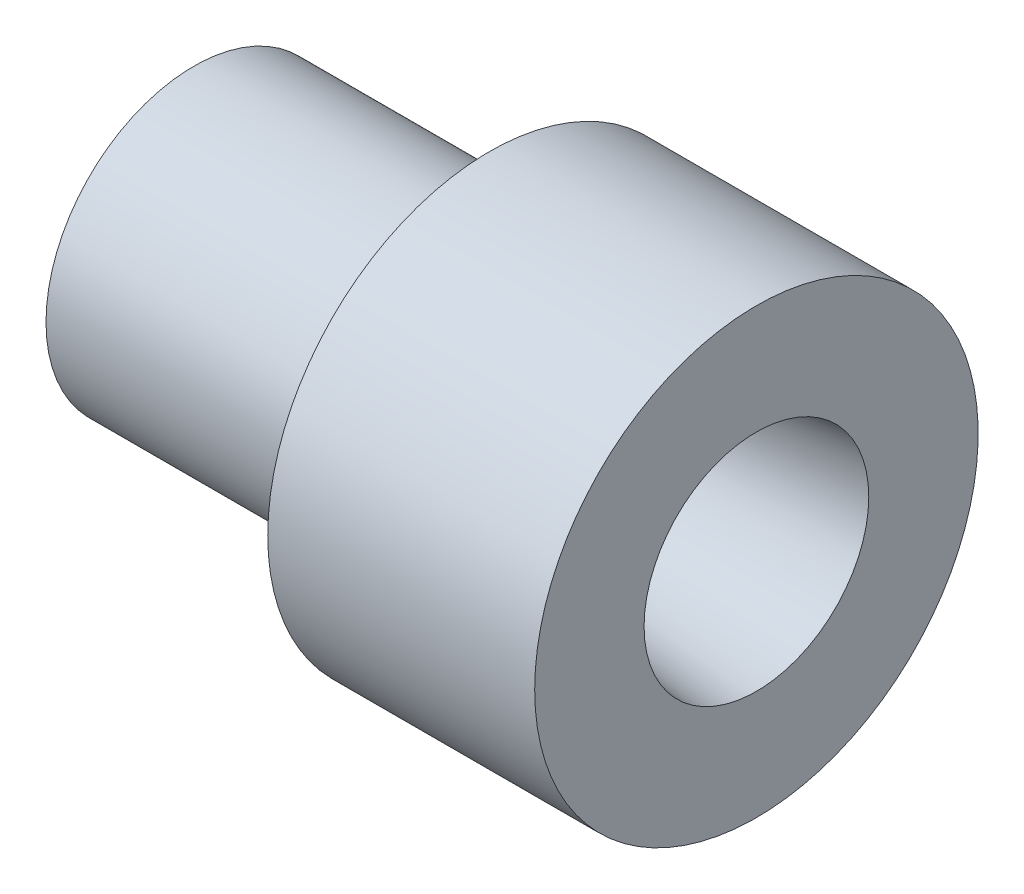
SolidWorks part; units mm, degrees
ref_plane "Front Plane" through (0, 0, 0) normal (0, 0, 1) x (1, 0, 0)
ref_plane "Top Plane" through (0, 0, 0) normal (0, 1, 0) x (1, 0, 0)
ref_plane "Right Plane" through (0, 0, 0) normal (1, 0, 0) x (0, 0, -1)
sketch "Sketch1" plane through (0, 0, 0) normal (0, 1, 0) x (1, 0, 0)
  line L0 (0, 0) -> (0, 2.286) construction
  line L1 (0, 2.286) -> (0, 6.35)
  line L2 (12.7, 9.525) -> (24.1665, 9.525)
  line L3 (24.1665, 9.525) -> (24.1665, 4.826)
  line L4 (24.1665, 4.826) -> (0, 2.286)
  line L5 (0, 0) -> (24.1665, 0) construction
  line L6 (24.1665, 0) -> (24.1665, 4.826) construction
  line L8 (12.7, 6.35) -> (12.7, 9.525)
  line L12 (0, 6.35) -> (12.7, 6.35)
  point P3 (0.1166, 6.35)
  point P6 (12.7, 6.35)
  point P11 (0, 6.35)
  point P12 (12.7, 7.1175)
  dimension "D1" = 2.286
  dimension "D2" = 4.826
  dimension "D3" = 6
  dimension "D4" = 9.525
  dimension "D5" = 6.35
  dimension "D6" = 12.7
revolve "Revolve1" add sketch "Sketch1" angle 360 about L5
equation "\"z\" = 8\t\t\t\t'number of blades"
equation "\"de\" = 0.43in\t\t\t'entrance eye diameter"
equation "\"de_length\" = 10mm\t\t'entrance eye consistent length"
equation "\"d_exit\" = 0.18in \t\t'throat aka d1"
equation "\"d2\" = 2.1in \t\t\t'outer diameter of the impeller"
equation "\"b2\" = .2in\t\t\t'tip height from disc surface at d2; slightly higher than d_exit"
equation "\"b1\" = \"b2\" + (\"d2\"/2 - \"de\"/2)*tan(\"theta\") \t\t\t'tip height from disc surface at inlet eye"
equation "\"theta\" = 12\t\t\t'angle of blades from inner to outer "
equation "\"ae\" = 3.14*(\"de\"^2)/4\t\t'entrance eye area'"
equation "\"ce\" = 3.14*\"de\"\t\t'entrance eye circumference"
equation "\"av_ratio\" = .325\t\t'ratio of av/ae at N_s of 470, range is .275 to .375, .325 ideal. High ratio means bigger area means smaller blades"
equation "\"av\" = \"ae\"*\"av_ratio\"\t\t'area between just two blades"
equation "\"s_open\" = \"av\"/\"b1\"\t\t'width of open area"
equation "\"s\"=\"ce\" - \"z\"*\"s_open\""
equation "\"min blade thickness\" = .15in"
equation "\"bearing OD\" = 30mm"
equation "\"bearing ID\"= 10mm"
equation "\"bearing depth\"= 9mm"
equation "\"bearing outer race thickness\"= 1mm"
equation "\"bearing inner race thickness\"= 1mm"
equation "\"bearing bore\" = \"bearing depth\" + 1mm"
equation "\"lower seal OD\" = .917in\t\t'this is https://www.mcmaster.com/#9281k121/=174001b"
equation "\"lower seal ID\"= .375in"
equation "\"lower seal depth\" = .625in + .218in"
equation "\"lower seal bore\" = \"lower seal depth\" + 1mm"
equation "\"upper seal OD\" = 1.125in\t'this is https://www.mcmaster.com/#5154t33/=173zuau, needs to be visually inspected before machining!"
equation "\"upper seal ID\"= 0.625in"
equation "\"upper seal depth\"= .25in\t'aka height; these values need to be confirmed by inspection!! We may want to compress the height."
equation "\"upper seal bore\" = \"upper seal depth\" + 1mm"
equation "\"big o-ring thickness\" = .139in"
equation "\"big o-ring OD\" = 2.734in"
equation "\"big o-ring ID\" = 3.012in"
equation "\"big o-ring groove depth\" = \"big o-ring thickness\"*4/5"
equation "\"impeller center height\" = \"impeller base thickness\" + \"b1\"\t'impeller height at de"
equation "\"impeller outer height\" = \"impeller base thickness\" + \"b2\"\t'impeller height at de"
equation "\"impeller upper clearance\"= .5mm"
equation "\"impeller horizontal clearance\"= (\"d2\"*1.15 - \"d2\")/2 \t\t'clearance based on D2-D3 ratio for circular volute, ranges 1.15 to 1.2"
equation "\"impeller bottom clearance\"= .5mm"
equation "\"impeller base thickness\"= 2mm"
equation "\"impeller dowel diameter\" = 2mm"
equation "\"impeller bolt head diameter\" = \"m4 head bore diameter\""
equation "\"impeller bolt head depth\" = 4mm"
equation "\"impeller bolt stop depth\" = 3mm"
equation "\"impeller bolt bore\" = \"m4 clearance\""
equation "\"impeller shaft bore depth\" = 12mm"
equation "\"impeller shaft bore\" = 8mm"
equation "\"impeller boss depth\" = \"impeller shaft bore depth\"+\"impeller bolt stop depth\"+\"impeller bolt head depth\"-\"impeller base thickness\""
equation "\"impeller boss diameter\" = \"upper seal ID\""
equation "\"impeller dowel length\" = 2mm*2 + \"impeller shaft bore\""
equation "\"coupler motor shaft hole ID\"= 8mm"
equation "\"coupler OD\"= 17mm"
equation "\"coupler length\"= 25mm"
equation "\"motor OD\" = 64mm"
equation "\"motor shaft diameter\"= 8mm"
equation "\"motor shaft pride\"= 32mm"
equation "\"motor to bearing plate distance\" = \"motor shaft pride\" + 2mm +\"coupler length\"/2"
equation "\"square plate bolt bore\" = \"m8 clearance\""
equation "\"square plate bolt head diameter\" = 13.5mm"
equation "\"square plate bolt head depth\" = 8mm"
equation "\"square plate bolt pattern diameter\"= 3.5in"
equation "\"motor mount center bore\"= \"coupler OD\"+ 4mm"
equation "\"motor mount post radius\"= ( 3 * \"square plate bolt bore\" ) / 2"
equation "\"motor mount m4 screw hole diameter\"= 4mm"
equation "\"motor mount m4 head diameter\"= 7.25mm"
equation "\"motor mount m4 head depth\"= 4mm"
equation "\"motor mount m4 pattern diamater\" = 30mm"
equation "\"motor mount plate thickness\"= 8mm + \"motor mount m4 head depth\""
equation "\"bearing plate stop ID\" = \"bearing OD\" - 4mm"
equation "\"bearing plate stop depth\" = 3mm"
equation "\"bearing plate thickness\" = \"bearing bore\" + \"bearing plate stop depth\" + \"shaft bearing stop length\""
equation "\"lower seal plate lip depth\" = 2mm"
equation "\"lower seal plate lip ID\" = \"lower seal OD\" - 3mm"
equation "\"lower seal plate thickness\" = \"lower seal plate lip depth\" + \"lower seal bore\""
equation "\"shaft coupler section diameter\" = 8mm"
equation "\"shaft coupler section length\" = \"motor to bearing plate distance\" - \"motor shaft pride\" - 2mm"
equation "\"shaft bearing section diameter\" = \"bearing ID\""
equation "\"shaft bearing section length\" = \"bearing plate stop depth\" + \"bearing depth\""
equation "\"shaft bearing stop diameter\" = \"bearing ID\" + 4mm"
equation "\"shaft bearing stop length\" = 3mm"
equation "\"shaft lower seal section diameter\" = \"lower seal ID\""
equation "\"shaft lower seal section length\" = \"lower seal plate thickness\" + 1mm"
equation "\"shaft impeller section diameter\" = \"impeller shaft bore\""
equation "\"shaft impeller section length\" = \"upper seal plate thickness\" + \"upper seal plate riser\" + \"impeller bottom clearance\" + \"impeller base thickness\" - \"impeller bolt head depth\" - \"impeller bolt stop depth\""
equation "\"upper seal plate thickness\" = \"upper seal plate pressure hole diameter\"+10mm"
equation "\"upper seal plate lip ID\" = \"upper seal OD\" - 3mm"
equation "\"upper seal plate riser\" = 6.59mm \t\t'this number needs to be read from the housing file"
equation "\"upper seal plate pressure hole diameter\" = .125in\t'this is 1/8 drill "
equation "\"upper seal plate pressure tap diameter\" = .328125in \t'this is 21/64 drill for a 1/8 ANPT tap"
equation "\"upper seal plate pressure tap grip\" = 5mm\t\t'this is the area around the tap so it doesn't crack"
equation "\"upper seal plate pressure tap depth\" = 12"
equation "\"impeller cavity center height\"= \"impeller bottom clearance\" + \"impeller upper clearance\" + \"impeller center height\""
equation "\"impeller cavity diameter\"= 2 * \"impeller horizontal clearance\" + \"d2\" \t\t\t\t\t\t\t\t\t'called D3 analytically"
equation "\"impeller cavity outer height\"= \"impeller bottom clearance\" + \"impeller upper clearance\" + \"impeller base thickness\" + \"b2\" \t\t'this is height at impeller diameter d2, not at d3"
equation "\"impeller housing thickness\"= \"impeller housing exit threaded diameter\" + 2*\"impeller housing outlet grip\""
equation "\"impeller housing diameter\" = \"square plate bolt pattern diameter\" + 2*\"motor mount post radius\""
equation "\"impeller housing bolt count\" = 8"
equation "\"impeller housing bolt diameter\" = \"m6 clearance\""
equation "\"impeller housing bolt pattern diameter\" = 3.5in"
equation "\"impeller housing threaded inlet diameter\" = 0.515625in \t'this is the 33/64 drill size for 9/16-18 fitting, expecting swagelok SS-8FK0-1-6STH fitting"
equation "\"impeller housing threaded inlet depth\"= 10mm"
equation "\"impeller housing exit threaded diameter\"= 0.515625in \t\t'this is the 33/64 drill size for 9/16-18 fitting, expecting swagelok SS-8FK0-1-6STH fitting"
equation "\"impeller housing exit threaded depth\"= 10mm"
equation "\"impeller housing diffuser conical angle\"=10"
equation "\"impeller housing diffuser tangent angle\"=5"
equation "\"impeller housing diffuser final diameter\" = .38in\t\t'aka d2'"
equation "\"impeller housing outlet grip\" = 5mm"
equation "\"end mill size\" = 0.375in\t'for 3/8 endmill"
equation "\"m4 clearance\" = 0.171875in \t'this is 11/64 bit for 4.36mm"
equation "\"m4 tap\" = 0.125in\t\t'this is 1/8 bit for 3.17mm"
equation "\"m4 head bore diameter\" = 7.5mm"
equation "\"m4 head bore depth\" = 5mm\t'actual is ~4mm"
equation "\"m6 clearance\" = 0.234375in\t'this is 15/64 bit = 5.95mm, could use 6mm bit, B bit for 6.04mm or 1/4 bit for 6.35mm"
equation "\"m6 tap\" = 5mm\t\t\t'5mm is appropriate, could use 13/64 or #5,6,7"
equation "\"m6 head bore diameter\" = 11mm\t\t"
equation "\"m6 head bore depth\" = 7mm\t'actual is 6mm"
equation "\"m8 clearance\" = 0.3125in\t'this is 5/16in for 7.93mm, could use 8mm, O,P, or 21/64"
equation "\"m8 tap\" = 0.265625in\t\t'this is 17/64 for 6.746875mm"
equation "\"m8 head bore diameter\" = 14mm"
equation "\"m8 head bore depth\" = 9mm\t'actual is 8mm"
equation "\"D1@Sketch1\"=\"d_exit\"/2"
equation "\"D2@Sketch1\"=\"impeller housing diffuser final diameter\"/2"
equation "\"diffuser cartridge OD\" =.75in"
equation "\"D4@Sketch1\"=\"diffuser cartridge OD\"/2"
